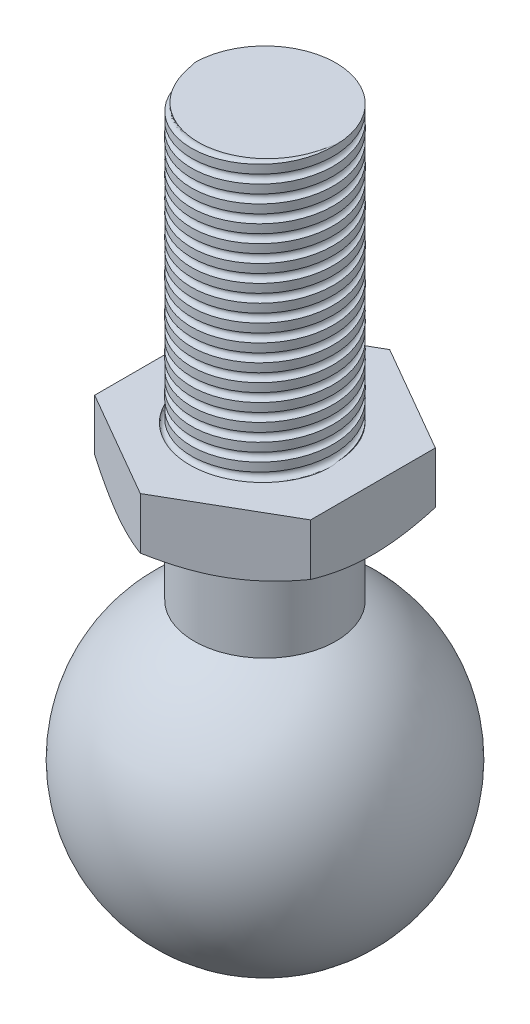
SolidWorks part; units mm, degrees
material "1.4401 (X5CrNiMo17-12-2)"
ref_plane "Ön Düzlem" through (0, 0, 0) normal (0, 0, 1) x (1, 0, 0)
ref_plane "Üst Düzlem" through (0, 0, 0) normal (0, 1, 0) x (1, 0, 0)
ref_plane "Sağ Düzlem" through (0, 0, 0) normal (1, 0, 0) x (0, 0, -1)
sketch "Çizim1" plane through (0, 0, 0) normal (1, 0, 0) x (0, 0, -1)
  line L0 (0, 9) -> (0, -9)
  arc A0 (0, 9) -> (0, -9) centre (0, 0) ccw
  dimension "D1" = 18
revolve "Döndür1" add sketch "Çizim1" angle 360 about L0
ref_plane "Düzlem1" through (0, 10, 0) normal (0, 1, 0) x (1, 0, 0)
sketch "Çizim2" plane through (0, 10, 0) normal (0, 1, 0) x (1, 0, 0)
  circle A0 centre (0, 0) radius 25
  dimension "D1" = 50
extrude "Kes-Ekstrüzyon1" cut sketch "Çizim2" against normal blind 2
sketch "Çizim3" plane through (0, 0, 0) normal (1, 0, 0) x (0, 0, -1)
  line L0 (0, 0) -> (0, 33) construction
  line L1 (0, 33) -> (-4.1231, 33)
  line L2 (-4.1231, 33) -> (-4.1231, 17)
  line L3 (-4.1231, 17) -> (-7.25, 17)
  line L4 (-7.25, 17) -> (-7.25, 14)
  line L5 (-7.25, 14) -> (-4.1231, 12.1947)
  line L6 (-4.1231, 12.1947) -> (-4.1231, 8)
  line L7 (-4.1231, 8) -> (-4.1231, 6.4246) construction
  line L8 (4.1231, 8) -> (-4.1231, 8) construction
  line L9 (-4.1231, 8) -> (0, 8)
  line L10 (0, 8) -> (0, 33)
  dimension "D1" = 16
  dimension "D2" = 25
  dimension "D3" = 3
  dimension "D4" = 120
  dimension "D5" = 7.25
revolve "Döndür2" add sketch "Çizim3" angle 360 about L10
sketch "Çizim4" plane through (0, 17, 0) normal (0, 1, 0) x (1, 0, 0)
  line L7 (0, 7.25) -> (-6.2787, 3.625)
  line L8 (-6.2787, 3.625) -> (-6.2787, -3.625)
  line L9 (-6.2787, -3.625) -> (0, -7.25)
  line L10 (0, -7.25) -> (6.2787, -3.625)
  line L11 (6.2787, -3.625) -> (6.2787, 3.625)
  line L12 (6.2787, 3.625) -> (0, 7.25)
  circle A1 centre (0, 0) radius 7.25 construction
  circle A2 centre (0, 0) radius 7.25
  circle A3 centre (0, 0) radius 7.25
  dimension "D1" = 0
extrude "Kes-Ekstrüzyon2" cut sketch "Çizim4" against normal blind 5
sketch "Çizim5" plane through (0, 33, 0) normal (0, 1, 0) x (1, 0, 0)
  circle A1 centre (0, 0) radius 4.1231
  circle A2 centre (0, 0) radius 4.1231
  dimension "D1" = 0
curve "Helis/Spiral1" pitch 1 height 17 turns 17
ref_plane "Düzlem2" through (0, 33, 4.1231) normal (-0.9993, -0.0386, 0) x (0, 0, 1)
sketch "Çizim6" plane through (0, 33, 4.1231) normal (-0.9993, -0.0386, 0) x (0, 0, 1)
  circle A0 centre (0, 0) radius 0.25
  dimension "D1" = 0.5
sweep "Kes-Süpür1" cut profiles "Çizim6" path "Helis/Spiral1"
